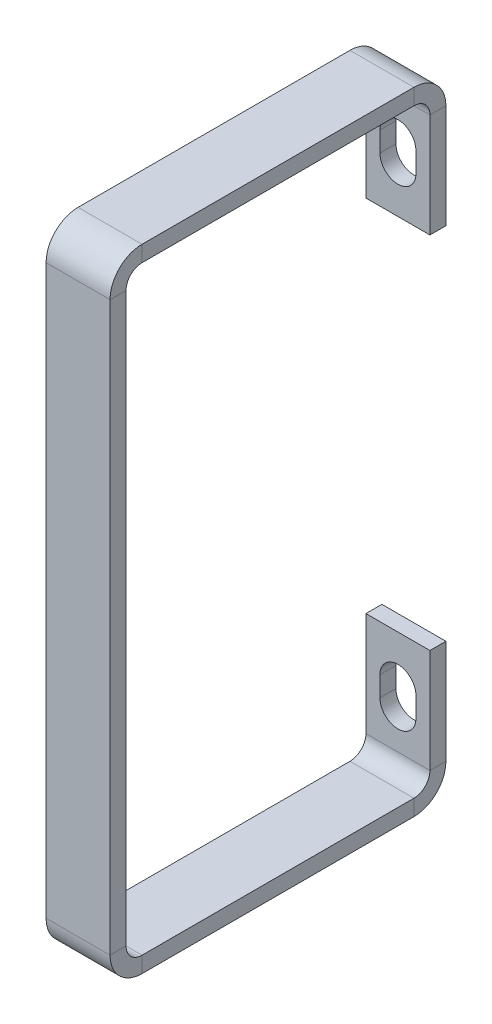
SolidWorks part; units mm, degrees
note: The reader was unsure of these and kept them because the rebuilt part matched: flange length of "Kante-Lasche3", "Kante-Lasche4".
material "3.0205 (EN-AW 1200)"
ref_plane "Front" through (0, 0, 0) normal (0, 0, 1) x (1, 0, 0)
ref_plane "Top" through (0, 0, 0) normal (0, 1, 0) x (1, 0, 0)
ref_plane "Right" through (0, 0, 0) normal (1, 0, 0) x (0, 0, -1)
sketch "Skizze1" plane through (0, 0, 0) normal (0, 0, 1) x (1, 0, 0)
  line L0 (0, 0) -> (0, 75)
  line L1 (0, 75) -> (8, 75)
  line L2 (8, 75) -> (8, 0)
  line L3 (8, 0) -> (0, 0)
  dimension "D1" = 8
  dimension "D2" = 75
base flange "Basis-Blech1" sketch "Skizze1" thickness 2 reverse thickness direction no parameters "D1"=5
ref_plane "Ebene1" through (0, 37.5, 0) normal (0, -1, 0) x (-1, 0, 0)
edge flange "Kante-Lasche3" sketch "Skizze18" flange angle 90 flange length 40 flange position material outside bend radius 2 thickness 2 relief obround parameters "D6"=10
sketch "Skizze18" plane through (0, 75, -2) normal (0, 1, 0) x (1, 0, 0)
  line L0 (8, 0) -> (0, 0) construction
  line L1 (8, 0) -> (0, 0)
  line L2 (0, 0) -> (0, 38)
  line L3 (0, 38) -> (8, 38)
  line L4 (8, 38) -> (8, 0)
  dimension "D1" = 38
bend "Kantenbiegung3" bend radius 2 bend angle 90 parameters "D5"=1
edge flange "Kante-Lasche4" sketch "Skizze21" flange angle 90 flange length 17 flange position material outside bend radius 2 thickness 2 relief obround parameters "D6"=10
sketch "Skizze21" plane through (0, 75, -40) normal (0, 0, 1) x (-1, 0, 0)
  line L2 (-8, 0) -> (-8, 15)
  line L3 (-8, 15) -> (0, 15)
  line L4 (0, 15) -> (0, 0)
  line L5 (0, 0) -> (-8, 0) construction
  line L6 (0, 0) -> (-8, 0)
  dimension "D1" = 15
bend "Kantenbiegung4" bend radius 2 bend angle 90 parameters "D5"=2
sketch "Skizze23" plane through (0, 0, -42) normal (0, 0, -1) x (-1, 0, 0)
  line L0 (0, 67) -> (-8, 67) construction
  line L3 (-4, 60) -> (-4, 60.9824) construction
  line L4 (0, 60) -> (-8, 60) construction
  line L5 (-4, 65.75) -> (-4, 68.25) construction
  line L6 (-6.25, 65.75) -> (-6.25, 68.25)
  line L7 (-1.75, 65.75) -> (-1.75, 68.25)
  arc A1 (-6.25, 65.75) -> (-1.75, 65.75) centre (-4, 65.75) ccw
  arc A2 (-1.75, 68.25) -> (-6.25, 68.25) centre (-4, 68.25) ccw
  point P12 (-4, 67)
  point P20 (-4, 70.5)
  point P21 (-4, 63.5)
  dimension "D1" = 4.5
  dimension "D2" = 7
  dimension "D3" = 7
extrude "Schnitt-Linear austragen1" cut sketch "Skizze23" against normal up to surface (2 mm away) normal cut yes up to face at (4, 66.5, -40)
mirror "Spiegeln1" about plane through (0, 37.5, 0) normal (0, -1, 0) of "Schnitt-Linear austragen1", "Kante-Lasche3", "Kante-Lasche4"
bend "Biegung spiegeln1" bend radius 2 bend angle 90 parameters "D5"=3
bend "Biegung spiegeln2" bend radius 2 bend angle 90 parameters "D5"=4
sketch "Biegung-Linien1" [suppressed] plane through (0, 0, 0) normal (0, 1, 0) x (1, 0, 0)
sketch "Rahmen1" [suppressed] plane through (0, 0, 0) normal (0, 1, 0) x (1, 0, 0)
sheet metal parameters "Blech1" thickness 2 parameters "D1"=5
flat pattern "Abwicklung1" [suppressed]
sketch "Biegung-Linien2" plane through (0, 0, 0) normal (0, 0, 1) x (1, 0, 0)
sketch3d "Rahmen2" [suppressed]
  line L0 (8, 75, 0) -> (8, 0, 0) construction
  line L1 (0, 75, 0) -> (0, 0, 0) construction
  line L2 (8, 75, 0) -> (0, 75, 0) construction
  line L3 (8, 0, 0) -> (0, 0, 0) construction
sheet metal parameters "Blech4" thickness 2 parameters "D1"=5
flat pattern "Abwicklung1"
sketch "Biegung-Linien2" plane through (0, 0, 0) normal (0, 0, 1) x (1, 0, 0)
  line L0 (10, 59.7124) -> (0, 59.7124) construction
  line L1 (10, 59.7124) -> (0, 59.7124) construction
sketch3d "Rahmen2" [suppressed]
  line L0 (10, 92.4248, 0) -> (10, 0, 0) construction
  line L1 (0, 92.4248, 0) -> (0, 0, 0) construction
  line L2 (10, 92.4248, 0) -> (0, 92.4248, 0) construction
  line L3 (10, 0, 0) -> (0, 0, 0) construction
bend of the flat pattern "Abwickeln-<Kantenbiegung3>1"
sheet metal parameters "Blech5" thickness 2 parameters "D1"=5
flat pattern "Abwicklung1"
sketch "Biegung-Linien2" plane through (0, 0, 0) normal (0, 0, 1) x (1, 0, 0)
  line L0 (10, 60.1416) -> (0, 60.1416) construction
  line L1 (10, 60.1416) -> (0, 60.1416) construction
  line L2 (10, 93.4248) -> (0, 93.4248) construction
  line L3 (10, 93.4248) -> (0, 93.4248) construction
sketch3d "Rahmen2" [suppressed]
  line L0 (10, 101.5664, 0) -> (10, 0, 0) construction
  line L1 (0, 101.5664, 0) -> (0, 0, 0) construction
  line L2 (10, 101.5664, 0) -> (0, 101.5664, 0) construction
  line L3 (10, 0, 0) -> (0, 0, 0) construction
bend of the flat pattern "Abwickeln-<Kantenbiegung3>1"
bend of the flat pattern "Abwickeln-<Kantenbiegung4>1"
sheet metal parameters "Blech6" thickness 2 parameters "D1"=5
flat pattern "Abwicklung1"
sketch "Biegung-Linien2" plane through (0, 0, 0) normal (0, 0, 1) x (1, 0, 0)
  line L0 (8, 75.3562) -> (0, 75.3562) construction
  line L1 (8, 75.3562) -> (0, 75.3562) construction
  line L2 (8, 114.0686) -> (0, 114.0686) construction
  line L3 (8, 114.0686) -> (0, 114.0686) construction
  line L4 (0, -39.0686) -> (8, -39.0686) construction
  line L5 (0, -0.3562) -> (8, -0.3562) construction
  line L6 (0, -39.0686) -> (8, -39.0686) construction
  line L7 (0, -0.3562) -> (8, -0.3562) construction
sketch3d "Rahmen2" [suppressed]
  line L0 (8, 129.4248, 0) -> (8, -54.4248, 0) construction
  line L1 (0, 129.4248, 0) -> (0, -54.4248, 0) construction
  line L2 (8, 129.4248, 0) -> (0, 129.4248, 0) construction
  line L3 (8, -54.4248, 0) -> (0, -54.4248, 0) construction
bend of the flat pattern "Abwickeln-<Kantenbiegung3>1"
bend of the flat pattern "Abwickeln-<Kantenbiegung4>1"
bend of the flat pattern "Abwickeln-<Biegung spiegeln1>1"
bend of the flat pattern "Abwickeln-<Biegung spiegeln2>1"
sheet metal parameters "Blech7" thickness 2 parameters "D1"=5
flat pattern "Abwicklung1"
sketch "Biegung-Linien2" plane through (0, 0, 0) normal (0, 0, 1) x (1, 0, 0)
  line L0 (10, 65.1416) -> (0, 65.1416) construction
  line L1 (10, 65.1416) -> (0, 65.1416) construction
  line L2 (10, 108.4248) -> (0, 108.4248) construction
  line L3 (10, 108.4248) -> (0, 108.4248) construction
  line L4 (0, -43.4248) -> (10, -43.4248) construction
  line L5 (0, -0.1416) -> (10, -0.1416) construction
  line L6 (0, -43.4248) -> (10, -43.4248) construction
  line L7 (0, -0.1416) -> (10, -0.1416) construction
sketch3d "Rahmen2" [suppressed]
  line L0 (10, 121.5664, 0) -> (10, -56.5664, 0) construction
  line L1 (0, 121.5664, 0) -> (0, -56.5664, 0) construction
  line L2 (10, 121.5664, 0) -> (0, 121.5664, 0) construction
  line L3 (10, -56.5664, 0) -> (0, -56.5664, 0) construction
bend of the flat pattern "Abwickeln-<Kantenbiegung3>1"
bend of the flat pattern "Abwickeln-<Kantenbiegung4>1"
